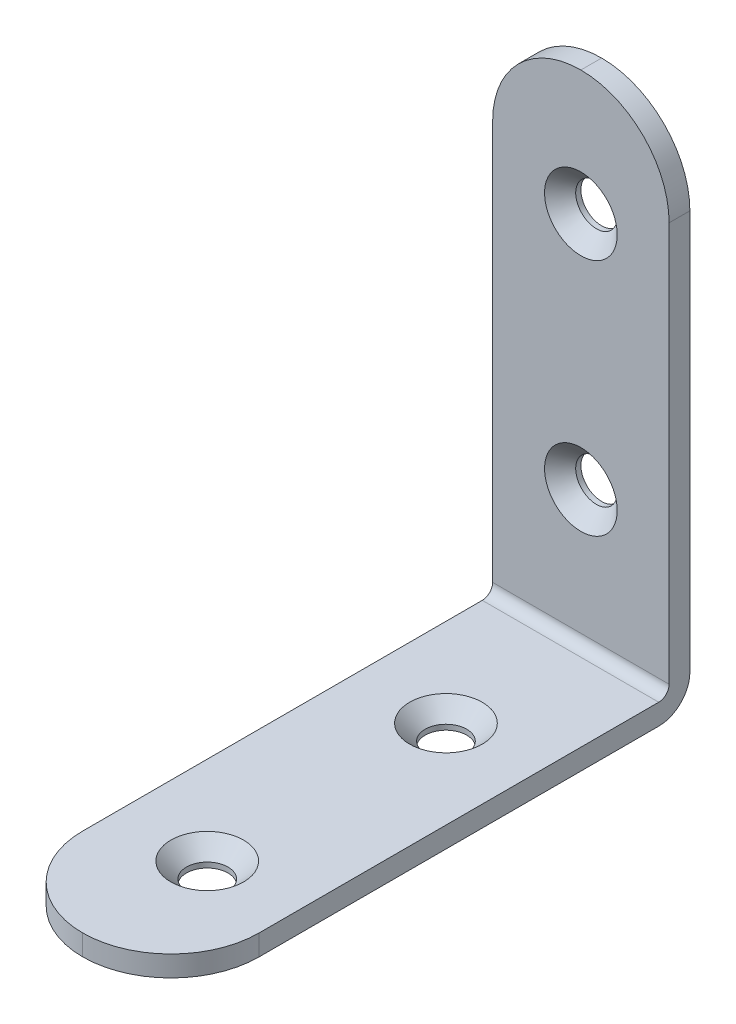
SolidWorks part; units mm, degrees
ref_plane "前视基准面" through (0, 0, 0) normal (0, 0, 1) x (1, 0, 0)
ref_plane "上视基准面" through (0, 0, 0) normal (0, 1, 0) x (1, 0, 0)
ref_plane "右视基准面" through (0, 0, 0) normal (1, 0, 0) x (0, 0, -1)
sketch "草图1" plane through (0, 0, 0) normal (1, 0, 0) x (0, 0, -1)
  line L0 (-50, 0) -> (-3, 0)
  line L1 (0, 3) -> (0, 50)
  line L2 (-50, 2) -> (-3, 2)
  line L3 (-2, 3) -> (-2, 50)
  line L4 (-50, 0) -> (-50, 2)
  line L5 (0, 50) -> (-2, 50)
  arc A0 (-3, 0) -> (0, 3) centre (-3, 3) ccw
  arc A1 (-3, 2) -> (-2, 3) centre (-3, 3) ccw
  point P10 (0, 0)
  dimension "D1" = 50
  dimension "D2" = 50
  dimension "D3" = 2
extrude "凸台-拉伸1" add sketch "草图1" along normal blind 8.5 and the other way blind 8.5
sketch "草图3" plane through (0, 2, 0) normal (0, 1, 0) x (1, 0, 0)
  line L0 (0, 5.2738) -> (0, -38.9564) construction
  line L1 (-8.5, 0) -> (8.5, 0) construction
  circle A0 centre (0, -38) radius 2
  circle A1 centre (0, -15) radius 2
  dimension "D1" = 4
  dimension "D2" = 15
  dimension "D4" = 23
  dimension "D3" = 2
extrude "切除-拉伸2" cut sketch "草图3" against normal blind 15.5
sketch "草图4" plane through (0, 0, 2) normal (0, 0, 1) x (1, 0, 0)
  line L0 (0, -4.5637) -> (0, 38) construction
  line L1 (-8.5, 0) -> (8.5, 0) construction
  circle A0 centre (0, 38) radius 2
  circle A1 centre (0, 15) radius 2
  dimension "D1" = 4
  dimension "D2" = 15
  dimension "D4" = 23
  dimension "D3" = 2
extrude "切除-拉伸3" cut sketch "草图4" against normal blind 15.5
fillet "圆角1" radius 8.5 4 edges at (8.5, 50, 1) (-8.5, 50, 1) (8.5, 1, 50) (-8.5, 1, 50)
chamfer "倒角1" distance 1.5 angle 45 4 edges at (2, 38, 2) (0, 2, 40) (0, 2, 17) (2, 15, 2)
